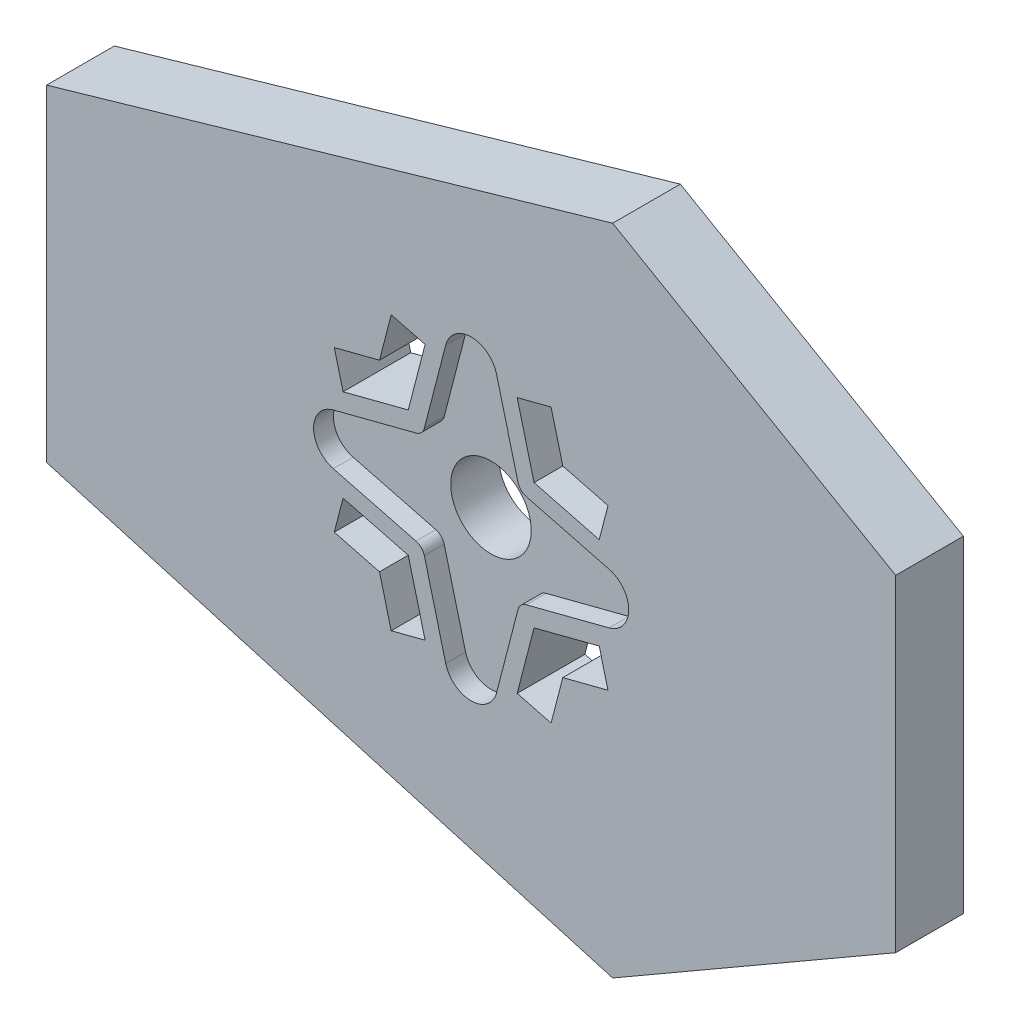
SolidWorks part; units mm, degrees
ref_plane "Front Plane" through (0, 0, 0) normal (0, 0, 1) x (1, 0, 0)
ref_plane "Top Plane" through (0, 0, 0) normal (0, 1, 0) x (1, 0, 0)
ref_plane "Right Plane" through (0, 0, 0) normal (1, 0, 0) x (0, 0, -1)
sketch "Sketch1" plane through (0, 0, 0) normal (0, 0, 1) x (1, 0, 0)
  line L0 (6.9744, -28) -> (-41.5231, -14) construction
  line L1 (-41.5231, 14) -> (-41.5231, -14) construction
  line L2 (-41.5231, 14) -> (6.9744, 28) construction
  line L3 (31.2231, 14) -> (6.9744, 28) construction
  line L4 (31.2231, -14) -> (31.2231, 14) construction
  line L5 (6.9744, -28) -> (31.2231, -14) construction
  line L6 (6.9744, -28) -> (-41.5231, -14)
  line L7 (-41.5231, 14) -> (-41.5231, -14)
  line L8 (-41.5231, 14) -> (6.9744, 28)
  line L9 (31.2231, 14) -> (6.9744, 28)
  line L10 (31.2231, -14) -> (31.2231, 14)
  line L11 (6.9744, -28) -> (31.2231, -14)
  line L20 (-2.9716, -11.813) -> (-1.1403, -4.7276)
  line L21 (-2.9716, -11.813) -> (-1.1403, -4.7276)
  line L22 (-0.4224, -4.0097) -> (6.663, -2.1784)
  line L23 (-0.4224, -4.0097) -> (6.663, -2.1784)
  line L24 (6.663, 2.1784) -> (-0.4224, 4.0097)
  line L25 (6.663, 2.1784) -> (-0.4224, 4.0097)
  line L26 (-1.1403, 4.7276) -> (-2.9716, 11.813)
  line L27 (-1.1403, 4.7276) -> (-2.9716, 11.813)
  line L28 (-7.3284, 11.813) -> (-9.1597, 4.7276)
  line L29 (-7.3284, 11.813) -> (-9.1597, 4.7276)
  line L30 (-9.8776, 4.0097) -> (-16.963, 2.1784)
  line L31 (-9.8776, 4.0097) -> (-16.963, 2.1784)
  line L32 (-16.963, -2.1784) -> (-9.8776, -4.0097)
  line L33 (-16.963, -2.1784) -> (-9.8776, -4.0097)
  line L34 (-9.1597, -4.7276) -> (-7.3284, -11.813)
  line L35 (-9.1597, -4.7276) -> (-7.3284, -11.813)
  circle A0 centre (-5.15, 0) radius 3.45 construction
  circle A1 centre (-5.15, 0) radius 3.45
  arc A9 (6.663, -2.1784) -> (6.663, 2.1784) centre (6.1, 0) ccw
  arc A11 (-2.9716, 11.813) -> (-7.3284, 11.813) centre (-5.15, 11.25) ccw
  arc A13 (-16.963, 2.1784) -> (-16.963, -2.1784) centre (-16.4, 0) ccw
  arc A15 (-7.3284, -11.813) -> (-2.9716, -11.813) centre (-5.15, -11.25) ccw
  arc A17 (6.663, -2.1784) -> (6.663, 2.1784) centre (6.1, 0) ccw
  arc A19 (-2.9716, 11.813) -> (-7.3284, 11.813) centre (-5.15, 11.25) ccw
  arc A21 (-16.963, 2.1784) -> (-16.963, -2.1784) centre (-16.4, 0) ccw
  arc A23 (-7.3284, -11.813) -> (-2.9716, -11.813) centre (-5.15, -11.25) ccw
  arc A30 (-0.4224, -4.0097) -> (-1.1403, -4.7276) centre (-0.1722, -4.9778) ccw
  arc A31 (-0.4224, -4.0097) -> (-1.1403, -4.7276) centre (-0.1722, -4.9778) ccw
  arc A32 (-1.1403, 4.7276) -> (-0.4224, 4.0097) centre (-0.1722, 4.9778) ccw
  arc A33 (-1.1403, 4.7276) -> (-0.4224, 4.0097) centre (-0.1722, 4.9778) ccw
  arc A34 (-9.8776, 4.0097) -> (-9.1597, 4.7276) centre (-10.1278, 4.9778) ccw
  arc A35 (-9.8776, 4.0097) -> (-9.1597, 4.7276) centre (-10.1278, 4.9778) ccw
  arc A36 (-9.1597, -4.7276) -> (-9.8776, -4.0097) centre (-10.1278, -4.9778) ccw
  arc A37 (-9.1597, -4.7276) -> (-9.8776, -4.0097) centre (-10.1278, -4.9778) ccw
  dimension "D1" = 0
extrude "Boss-Extrude1" add sketch "Sketch1" along normal up to surface (4.1 mm away) contours L8 L9 L10 L11 L6 L7 | A1
extrude "Boss-Extrude2" add sketch "Sketch1<3>" along normal up to surface (5.8 mm away) contours L6 L11 L10 L9 L8 L7 A23 A21 A19 A17 region at (-17.0197, -20.118, 0)
sketch "Sketch1<3>" plane through (0, 0, 0) normal (0, 0, 1) x (1, 0, 0) same geometry as "Sketch1"
sketch "Sketch3" plane through (0, 0, 5.8) normal (0, 0, 1) x (1, 0, 0)
  line L0 (-13.0004, 7.8504) -> (-16.8732, 6.8495) construction
  line L1 (-16.8732, 6.8495) -> (-16.1225, 3.9449) construction
  line L2 (-10.5382, 5.3882) -> (-16.1225, 3.9449) construction
  line L3 (-9.0949, 10.9725) -> (-10.5382, 5.3882) construction
  line L4 (-11.9995, 11.7232) -> (-9.0949, 10.9725) construction
  line L5 (-11.9995, 11.7232) -> (-13.0004, 7.8504) construction
  line L6 (-13.0004, 7.8504) -> (-16.8732, 6.8495)
  line L7 (-16.8732, 6.8495) -> (-16.1225, 3.9449)
  line L8 (-10.5382, 5.3882) -> (-16.1225, 3.9449)
  line L9 (-9.0949, 10.9725) -> (-10.5382, 5.3882)
  line L10 (-11.9995, 11.7232) -> (-9.0949, 10.9725)
  line L11 (-11.9995, 11.7232) -> (-13.0004, 7.8504)
extrude "Cut-Extrude1" cut sketch "Sketch3" against normal through all
sketch "Sketch4" plane through (0, 0, 5.8) normal (0, 0, 1) x (1, 0, 0)
  line L0 (-5.15, 13.5) -> (-5.15, -13.5) construction
  line L1 (-18.65, 0) -> (8.35, 0) construction
  arc A0 (-2.9716, 11.813) -> (-7.3284, 11.813) centre (-5.15, 11.25) ccw construction
  arc A1 (-7.3284, -11.813) -> (-2.9716, -11.813) centre (-5.15, -11.25) ccw construction
  arc A2 (-16.963, 2.1784) -> (-16.963, -2.1784) centre (-16.4, 0) ccw construction
  arc A3 (6.663, -2.1784) -> (6.663, 2.1784) centre (6.1, 0) ccw construction
ref_plane "Plane1" through (-5.15, 0, 0) normal (-1, 0, 0) x (0, -1, 0)
ref_plane "Plane2" through (0, 0, 0) normal (0, -1, 0) x (1, 0, 0)
mirror "Mirror1" about plane through (-5.15, 0, 0) normal (-1, 0, 0) of "Cut-Extrude1"
mirror "Mirror2" about plane through (0, 0, 0) normal (0, -1, 0) of "Cut-Extrude1", "Mirror1"
